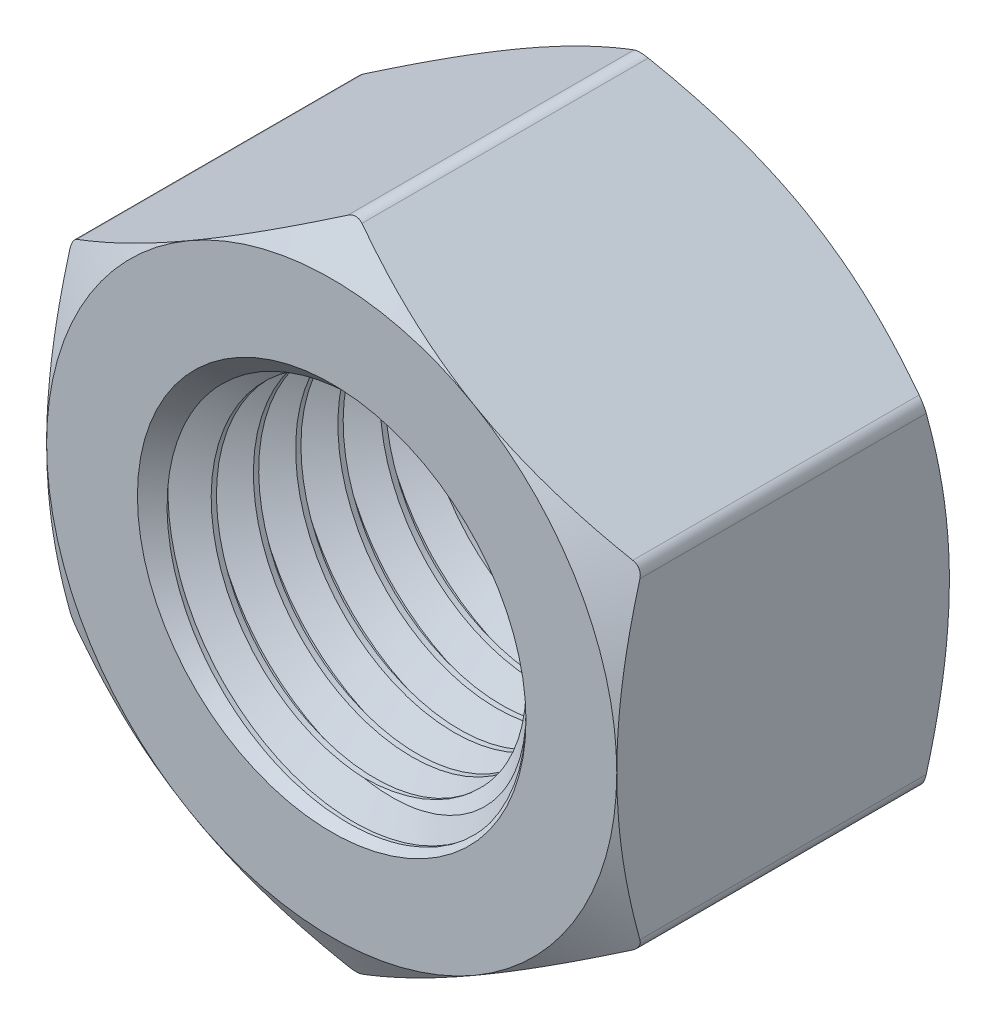
SolidWorks part; units mm, degrees
ref_plane "Front" through (0, 0, 0) normal (0, 0, 1) x (1, 0, 0)
ref_plane "Top" through (0, 0, 0) normal (0, 1, 0) x (1, 0, 0)
ref_plane "Right" through (0, 0, 0) normal (1, 0, 0) x (0, 0, -1)
sketch "Sketch1" plane through (0, 0, 0) normal (0, 0, 1) x (1, 0, 0)
  line L0 (0, 4.7625) -> (0, 3.7042) construction
  line L1 (-7.1437, 4.1244) -> (-7.1437, -4.1244)
  line L2 (-7.1437, -4.1244) -> (0, -8.2489)
  line L3 (0, -8.2489) -> (7.1437, -4.1244)
  line L4 (7.1437, -4.1244) -> (7.1437, 4.1244)
  line L5 (7.1437, 4.1244) -> (0, 8.2489)
  line L6 (0, 8.2489) -> (-7.1437, 4.1244)
  circle A0 centre (0, 0) radius 7.1438 construction
  circle A1 centre (0, 0) radius 4.7625 construction
  point P10 (0, 4.7625)
  dimension "Width" = 14.2875
  dimension "Thread Size" = 9.525
  dimension "Thread Pitch" = 1.0583
sketch "Sketch2" plane through (0, 0, 0) normal (1, 0, 0) x (0, 0, -1)
  line L0 (-4.1672, 0) -> (4.1672, 0) construction
  line L1 (-4.1672, 8.2489) -> (4.1672, 8.2489) construction
  dimension "Height" = 8.3344
sketch "Sketch15" plane through (0, 0, 0) normal (0, 0, 1) x (1, 0, 0)
  line L1 (0, 8.2489) -> (-7.1437, 4.1244)
  line L2 (-7.1437, 4.1244) -> (-7.1438, -4.1244)
  line L3 (-7.1438, -4.1244) -> (0, -8.2489)
  line L4 (0, -8.2489) -> (7.1438, -4.1244)
  line L5 (7.1438, -4.1244) -> (7.1438, 4.1244)
  line L6 (7.1438, 4.1244) -> (0, 8.2489)
  circle A0 centre (0, 0) radius 7.1438 construction
extrude "Boss-Extrude2" add sketch "Sketch15" along normal mid plane 8.3344
sketch "Sketch16" plane through (0, 0, 0) normal (0, 0, 1) x (1, 0, 0)
  circle A0 centre (0, 0) radius 4.7625 construction
  circle A1 centre (0, 0) radius 4.7625
sketch "Sketch4" plane through (0, 0, -4.1672) normal (0, 0, -1) x (-1, 0, 0)
  circle A0 centre (0, 0) radius 4.7625 construction
  circle A1 centre (0, 0) radius 4.7625
extrude "Cut-Extrude4" cut sketch "Sketch16" against normal through all both and the other way through all
sketch "Sketch7" plane through (0, 0, 4.1672) normal (0, 0, 1) x (1, 0, 0)
  circle A0 centre (0, 0) radius 7.1438 construction
  circle A1 centre (0, 0) radius 7.1438
extrude "Cut-Extrude5" cut sketch "Sketch7" against normal through all draft 60 flip side to cut
mirror "Mirror4" about plane through (0, 0, 0) normal (0, 0, 1) of "Cut-Extrude5"
fillet "Fillet2" radius 0.3572 6 edges at (-7.1437, 4.1244, 0) (-7.1438, -4.1244, 0) (0, -8.2489, 0) (7.1438, -4.1244, 0) (7.1438, 4.1244, 0) (0, 8.2489, 0)
sketch "Sketch8" plane through (0, 0, 4.1672) normal (0, 0, 1) x (1, 0, 0)
  line L0 (1.2326, -4.6002) -> (0, 0) construction
  line L2 (0, 4.7625) -> (0, 3.7042) construction
  circle A0 centre (0, 0) radius 4.7625 construction
  point P0 (1.2326, -4.6002)
  dimension "D1" = 15
sketch "Sketch13" plane through (0, 0, -4.1672) normal (0, 0, -1) x (-1, 0, 0)
  circle A0 centre (0, 0) radius 4.7625 construction
  circle A1 centre (0, 0) radius 4.7625
extrude "Boss-Extrude1" add sketch "Sketch13" against normal up to surface (8.3344 mm away) separate body up to face at (4.7625, 0, 4.1672)
curve "Helix/Spiral3" pitch 1.0583 height 9.3927 radius 4.7625 centre (0, 0, -4.1672) axis (0, 0, 1) start towards (0, 1, 0)
sketch "Sketch12" plane through (0, 0, 0) normal (1, 0, 0) x (0, 0, -1)
  line L0 (5.0932, 4.7625) -> (4.1672, 4.7625)
  line L1 (5.0932, 4.7625) -> (4.6964, 4.0751)
  line L2 (4.6964, 4.0751) -> (4.5641, 4.0751)
  line L3 (4.5641, 4.0751) -> (4.1672, 4.7625)
  line L4 (4.6302, 4.0751) -> (4.6302, 4.7625) construction
  line L5 (4.3656, 4.4188) -> (4.8948, 4.4188) construction
  dimension "D1" = 60
  dimension "D2" = 0.1323
  dimension "D3" = 0.5292
sweep "Cut-Sweep1" cut profiles "Sketch12" path "Helix/Spiral3" align with end faces yes
sketch "Sketch17" plane through (0, 0, 4.1672) normal (0, 0, 1) x (1, 0, 0)
  circle A1 centre (0, 0) radius 4.7625
  circle A2 centre (0, 0) radius 4.7625
  dimension "D1" = 0
extrude "Boss-Extrude3" add sketch "Sketch17" against normal up to surface (8.3344 mm away) up to face at (4.7625, 0, -4.1672)
combine bodies "Combine1" operation type subtract main body 127 bodies to subtract 118
sketch "Sketch10" plane through (0, 0, 4.1672) normal (0, 0, 1) x (1, 0, 0)
  circle A0 centre (0, 0) radius 4.7625 construction
  circle A1 centre (0, 0) radius 4.7625 construction
  circle A2 centre (0, 0) radius 4.8683
  dimension "D1" = 0.1058
extrude "Cut-Extrude2" cut sketch "Sketch10" against normal through all draft 45
sketch "Sketch11" plane through (0, 0, -4.1672) normal (0, 0, -1) x (-1, 0, 0)
  circle A1 centre (0, 0) radius 4.8683 construction
  circle A2 centre (0, 0) radius 4.8683
extrude "Cut-Extrude3" cut sketch "Sketch11" against normal through all draft 45
equation "\"D1\"= \"Height@Sketch2\""
equation "\"D3@Helix/Spiral3\"=\"Height@Sketch2\"+\"Thread Pitch@Sketch1\""
equation "\"D4@Helix/Spiral3\"=\"Thread Pitch@Sketch1\""
equation "\"D2@Sketch12\" = \"D4@Helix/Spiral3\"*.125"
equation "\"D3@Sketch12\" = \"D4@Helix/Spiral3\"*.50"
equation "\"D1@Boss-Extrude2\"=\"Height@Sketch2\""
equation "\"D1@Fillet2\"=\"Width@Sketch1\"*0.025"
equation "\"D1@Sketch10\"=\"Thread Pitch@Sketch1\"*0.1"
